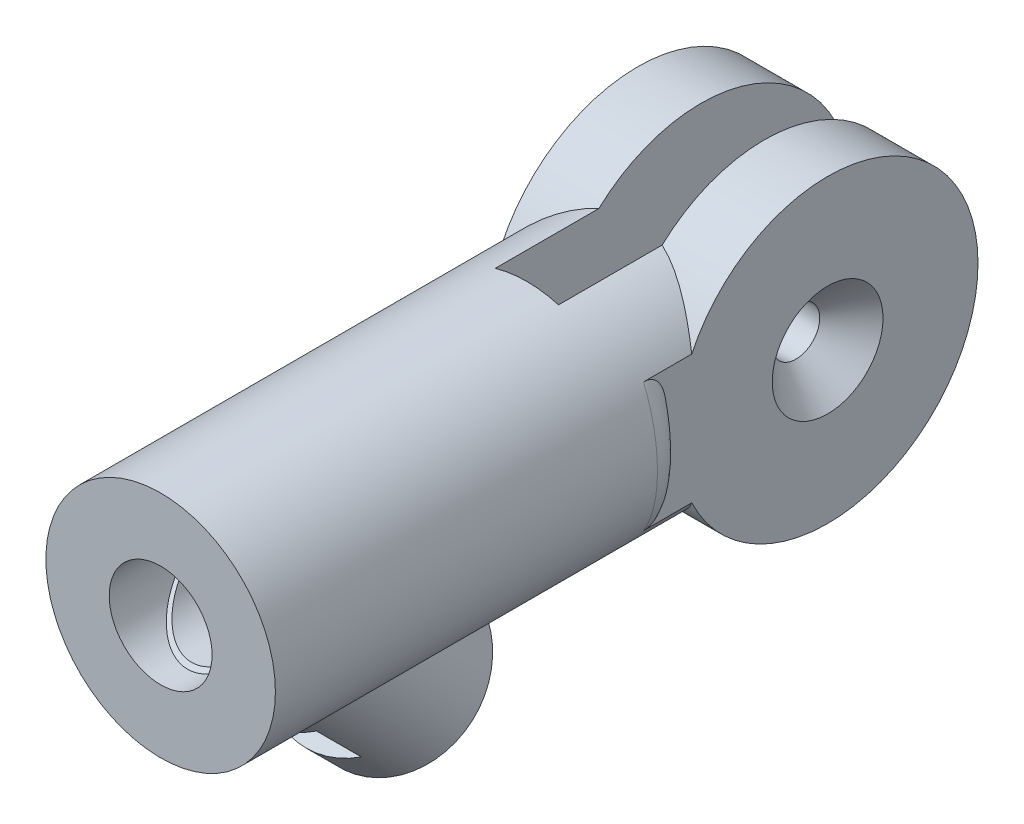
SolidWorks part; units mm, degrees
ref_plane "Спереди" through (0, 0, 0) normal (0, 0, 1) x (1, 0, 0)
ref_plane "Сверху" through (0, 0, 0) normal (0, 1, 0) x (1, 0, 0)
ref_plane "Справа" through (0, 0, 0) normal (1, 0, 0) x (0, 0, -1)
sketch "Sketch1" plane through (0, 0, 0) normal (0, 0, 1) x (1, 0, 0)
  circle A0 centre (0, 0) radius 3.25
  circle A1 centre (0, 0) radius 7.25
  dimension "D1" = 6.5
  dimension "D2" = 4
extrude "Boss-Extrude1" add sketch "Sketch1" along normal blind 30
sketch "Sketch2" plane through (0, 0, 0) normal (1, 0, 0) x (0, 0, -1)
  circle A0 centre (6.139, 0) radius 9.5
  dimension "D1" = 19
extrude "Boss-Extrude2" add sketch "Sketch2" along normal mid plane 12
sketch "Sketch4" plane through (-6, 0, 0) normal (-1, 0, 0) x (0, 0, 1)
  circle A0 centre (-6.139, 0) radius 1.5
  dimension "D1" = 3
extrude "Cut-Extrude1" cut sketch "Sketch4" against normal mid plane 34
sketch "Sketch5" plane through (6, 0, 0) normal (1, 0, 0) x (0, 0, -1)
  circle A0 centre (6.139, 0) radius 10
extrude "Cut-Extrude2" cut sketch "Sketch5" along normal blind 31
sketch "Sketch6" plane through (-6, 0, 0) normal (-1, 0, 0) x (0, 0, 1)
  circle A0 centre (-6.139, 0) radius 10
extrude "Cut-Extrude3" cut sketch "Sketch6" along normal blind 25
fillet "Fillet3" radius 2 2 edges at (7.2499, -0.0454, 3.8609) (-7.2499, 0.0454, 3.8609)
sketch "Sketch7" plane through (0, 0, 0) normal (1, 0, 0) x (0, 0, -1)
  line L1 (19.139, -13) -> (-6.861, -13)
  line L2 (19.139, -13) -> (19.139, 13)
  line L3 (19.139, 13) -> (-6.861, 13)
  line L4 (-6.861, -13) -> (-6.861, 13)
  line L5 (19.139, -13) -> (-6.861, 13) construction
  line L6 (19.139, 13) -> (-6.861, -13) construction
  point P0 (6.139, 0)
  dimension "D1" = 26
extrude "Cut-Extrude4" cut sketch "Sketch7" against normal mid plane 4
sketch "Sketch8" plane through (0, 0, 0) normal (1, 0, 0) x (0, 0, -1)
  line L0 (-33.2006, 0) -> (-12.6296, 0) construction
  line L1 (-25.0463, 0) -> (-12.2665, -12.7799) construction
  line L2 (-25.0463, 0) -> (-28.5819, -3.5355)
  line L3 (-28.5819, -3.5355) -> (-18.6824, -13.435)
  line L4 (-18.6824, -13.435) -> (-15.1468, -9.8995)
  line L5 (-15.1468, -9.8995) -> (-25.0463, 0)
  dimension "D1" = 45
  dimension "D2" = 5
  dimension "D3" = 14
revolve "Revolve1" add sketch "Sketch8" angle 360 about L1
sketch "Sketch9" plane through (0, 2.6237, 2.6237) normal (0, -0.7071, -0.7071) x (1, 0, 0)
  circle A0 centre (0, 17.7104) radius 1.5
  dimension "D1" = 3
extrude "Cut-Extrude5" cut sketch "Sketch9" against normal blind 15
sketch "Sketch10" plane through (0, 0, 30) normal (0, 0, 1) x (1, 0, 0)
  circle A0 centre (0, 0) radius 3
  dimension "D1" = 6
extrude "Cut-Extrude6" cut sketch "Sketch10" against normal blind 20
ref_plane "Plane1" through (0, 4.745, 4.745) normal (0, -0.7071, -0.7071) x (-1, 0, 0)
sketch "Sketch11" plane through (0, 4.745, 4.745) normal (0, -0.7071, -0.7071) x (-1, 0, 0)
  line L0 (-2.85, -19.3559) -> (-2.85, -33.9247)
  line L1 (0, -14.4195) -> (-2.85, -16.065)
  line L2 (-2.85, -16.065) -> (-2.85, -19.3559)
  line L3 (-2.85, -19.3559) -> (0, -21.0013)
  line L4 (0, -21.0013) -> (2.85, -19.3559)
  line L5 (2.85, -19.3559) -> (2.85, -16.065)
  line L6 (2.85, -16.065) -> (0, -14.4195)
  line L7 (-2.85, -33.9247) -> (2.85, -33.9247)
  line L8 (2.85, -33.9247) -> (2.85, -19.3559)
  circle A0 centre (0, -17.7104) radius 2.85 construction
  dimension "D1" = 5.7
extrude "Cut-Extrude7" cut sketch "Sketch11" against normal blind 3 contours L7 L8 L4 L3 L0 | L5 L6 L1 L2 L3 L4 region at (0, -14.3776, 23.8676) region at (0, -7.7782, 17.2682)
chamfer "Chamfer1" distance 1 angle 45 1 edges at (0, -9.1924, 22.925)
chamfer "Chamfer2" distance 2 angle 45 2 edges at (-6, 0, -7.639) (6, 0, -7.639)
sketch "Sketch12" plane through (0, 2.6237, 2.6237) normal (0, -0.7071, -0.7071) x (1, 0, 0)
  circle A0 centre (0, 17.7104) radius 5
extrude "Cut-Extrude8" cut sketch "Sketch12" along normal blind 15
